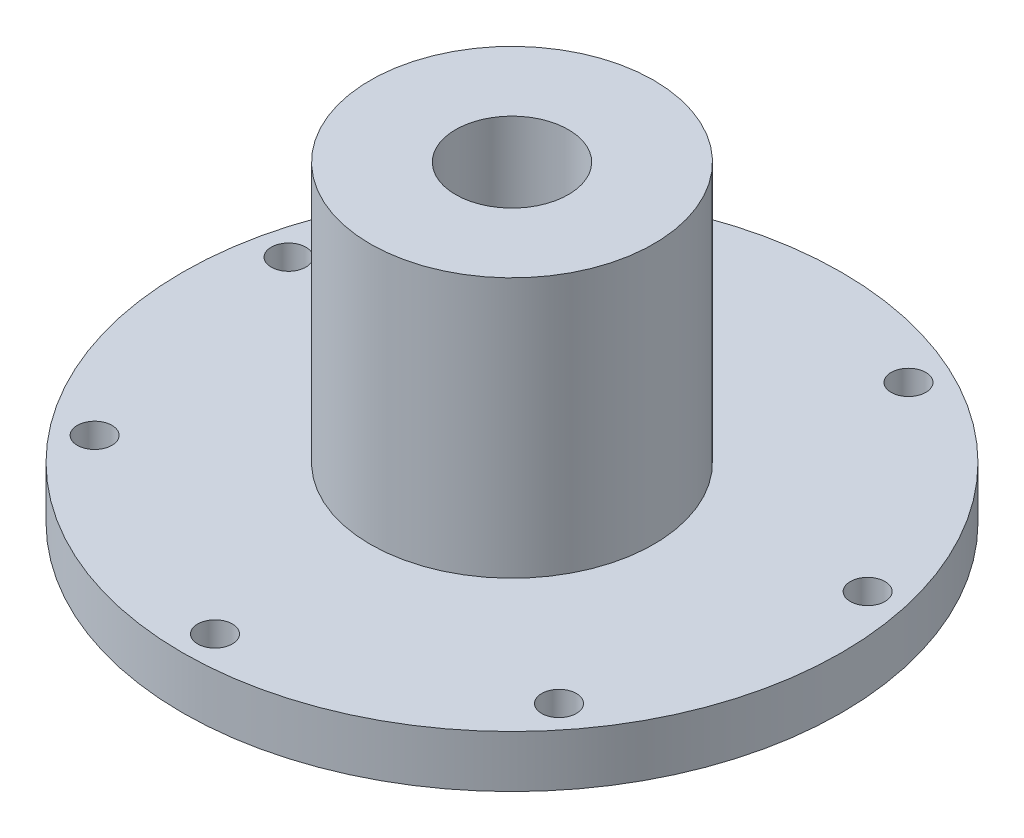
SolidWorks part; units mm, degrees
ref_plane "Front Plane" through (0, 0, 0) normal (0, 0, 1) x (1, 0, 0)
ref_plane "Top Plane" through (0, 0, 0) normal (0, 1, 0) x (1, 0, 0)
ref_plane "Right Plane" through (0, 0, 0) normal (1, 0, 0) x (0, 0, -1)
sketch "Sketch1" plane through (0, 0, 0) normal (0, 1, 0) x (1, 0, 0)
  circle A0 centre (0, 0) radius 3.25
  circle A1 centre (0, 0) radius 8.175
  circle A2 centre (0, 0) radius 19
  point P25 (0, 0)
extrude "Boss-Extrude1" add sketch "Sketch1" along normal blind 15 and the other way blind 3 contours A1 A0 region at (-7.9438, 0, 0)
extrude "Boss-Extrude2" add sketch "Sketch1<3>" against normal blind 3 separate body contours A2 A1 region at (-18.4626, 0, 0)
sketch "Sketch1<3>" plane through (0, 0, 0) normal (0, 1, 0) x (1, 0, 0) same geometry as "Sketch1"
sketch "Sketch2" plane through (0, 0, 0) normal (1, 0, 0) x (0, 0, -1)
  circle A0 centre (0, 6.7029) radius 2.5
extrude "Cut-Extrude1" cut sketch "Sketch2" against normal blind 15
sketch "Sketch3" plane through (0, -3, 0) normal (0, -1, 0) x (1, 0, 0)
  circle A1 centre (0, 17.1255) radius 1
  circle A2 centre (13.3892, 10.6776) radius 1
  circle A3 centre (16.6961, -3.8108) radius 1
  circle A4 centre (7.4305, -15.4295) radius 1
  circle A5 centre (-7.4305, -15.4295) radius 1
  circle A6 centre (-16.6961, -3.8108) radius 1
  circle A7 centre (-13.3892, 10.6776) radius 1
  point P14 (0, 0)
  dimension "D1" = 7
extrude "Cut-Extrude2" cut sketch "Sketch3" against normal through all and the other way through all
sketch "Sketch4" plane through (0, -3, 0) normal (0, -1, 0) x (1, 0, 0)
  circle A0 centre (0, 0) radius 4.175
extrude "Boss-Extrude4" add sketch "Sketch4" along normal blind 10 contours A0
extrude "Cut-Extrude3" cut sketch "Sketch1<5>" against normal blind 13 and the other way blind 15 contours A0
sketch "Sketch1<5>" plane through (0, 0, 0) normal (0, 1, 0) x (1, 0, 0) same geometry as "Sketch1"
